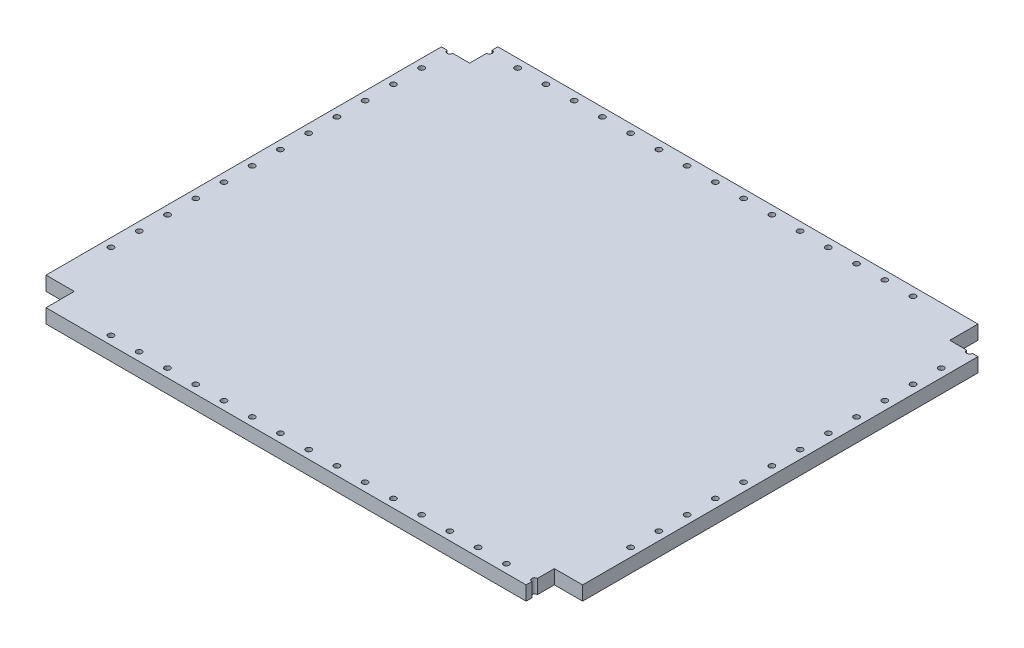
SolidWorks part; units mm, degrees
ref_plane "Front Plane" through (0, 0, 0) normal (0, 0, 1) x (1, 0, 0)
ref_plane "Top Plane" through (0, 0, 0) normal (0, 1, 0) x (1, 0, 0)
ref_plane "Right Plane" through (0, 0, 0) normal (1, 0, 0) x (0, 0, -1)
sketch "Sketch1" plane through (0, 0, 0) normal (0, 1, 0) x (1, 0, 0)
  line L1 (-241.3, -203.2) -> (241.3, -203.2)
  line L2 (-241.3, -203.2) -> (-241.3, 203.2)
  line L3 (-241.3, 203.2) -> (241.3, 203.2)
  line L4 (241.3, -203.2) -> (241.3, 203.2)
  line L5 (-241.3, -203.2) -> (241.3, 203.2) construction
  line L6 (-241.3, 203.2) -> (241.3, -203.2) construction
  point P0 (0, 0)
  dimension "D1" = 482.6
  dimension "D2" = 406.4
extrude "Boss-Extrude1" add sketch "Sketch1" along normal blind 12.7
sketch "Sketch2" plane through (0, 12.7, 0) normal (0, 1, 0) x (1, 0, 0)
  line L0 (241.3, 203.2) -> (-241.3, 203.2) construction
  line L1 (-241.3, 203.2) -> (-241.3, -203.2) construction
  circle A0 centre (-233.68, 177.8) radius 2.5
  dimension "D1" = 5
  dimension "D2" = 25.4
  dimension "D3" = 7.62
extrude "Cut-Extrude1" cut sketch "Sketch2" against normal through all
pattern_linear "LPattern1" count 13 spacing 25.4 along (0, 0, 1) of "Cut-Extrude1"
sketch "Sketch3" plane through (0, 12.7, 0) normal (0, 1, 0) x (1, 0, 0)
  line L0 (241.3, 203.2) -> (-241.3, 203.2) construction
  line L1 (-241.3, 203.2) -> (-241.3, -203.2) construction
  circle A0 centre (-215.9, 195.58) radius 2.5
  dimension "D1" = 5
  dimension "D2" = 7.62
  dimension "D3" = 25.4
extrude "Cut-Extrude2" cut sketch "Sketch3" against normal through all
pattern_linear "LPattern2" count 16 spacing 25.4 along (1, 0, 0) of "Cut-Extrude2"
sketch "Sketch4" plane through (0, 12.7, 0) normal (0, 1, 0) x (1, 0, 0)
  line L0 (241.3, -203.2) -> (241.3, 203.2) construction
  line L1 (241.3, 203.2) -> (-241.3, 203.2) construction
  circle A0 centre (233.68, 177.8) radius 2.5
  dimension "D1" = 5
  dimension "D2" = 7.62
  dimension "D3" = 25.4
extrude "Cut-Extrude3" cut sketch "Sketch4" against normal through all
pattern_linear "LPattern3" count 13 spacing 25.4 along (0, 0, 1) of "Cut-Extrude3"
sketch "Sketch5" plane through (0, 12.7, 0) normal (0, 1, 0) x (1, 0, 0)
  line L0 (241.3, -203.2) -> (241.3, 203.2) construction
  line L1 (-241.3, -203.2) -> (241.3, -203.2) construction
  circle A0 centre (215.9, -195.58) radius 2.5
  dimension "D1" = 5
  dimension "D2" = 25.4
  dimension "D3" = 7.62
extrude "Cut-Extrude4" cut sketch "Sketch5" against normal through all
pattern_linear "LPattern4" count 16 spacing 25.4 along (-1, 0, 0) of "Cut-Extrude4"
sketch "Sketch6" plane through (0, 12.7, 0) normal (0, 1, 0) x (1, 0, 0)
  line L1 (-241.3, 203.2) -> (-215.9, 203.2)
  line L2 (-241.3, 203.2) -> (-241.3, 177.8)
  line L3 (-241.3, 177.8) -> (-215.9, 177.8)
  line L4 (-215.9, 203.2) -> (-215.9, 177.8)
  dimension "D1" = 25.4
  dimension "D2" = 25.4
extrude "Cut-Extrude5" cut sketch "Sketch6" against normal through all
sketch "Sketch7" plane through (0, 12.7, 0) normal (0, 1, 0) x (1, 0, 0)
  line L1 (-241.3, -203.2) -> (-215.9, -203.2)
  line L2 (-241.3, -203.2) -> (-241.3, -177.8)
  line L3 (-241.3, -177.8) -> (-215.9, -177.8)
  line L4 (-215.9, -203.2) -> (-215.9, -177.8)
  dimension "D1" = 25.4
  dimension "D2" = 25.4
extrude "Cut-Extrude6" cut sketch "Sketch7" against normal through all
sketch "Sketch8" plane through (0, 12.7, 0) normal (0, 1, 0) x (1, 0, 0)
  line L1 (241.3, -203.2) -> (215.9, -203.2)
  line L2 (241.3, -203.2) -> (241.3, -177.8)
  line L3 (241.3, -177.8) -> (215.9, -177.8)
  line L4 (215.9, -203.2) -> (215.9, -177.8)
  dimension "D1" = 25.4
  dimension "D2" = 25.4
extrude "Cut-Extrude7" cut sketch "Sketch8" against normal through all
sketch "Sketch9" plane through (0, 12.7, 0) normal (0, 1, 0) x (1, 0, 0)
  line L1 (241.3, 203.2) -> (215.9, 203.2)
  line L2 (241.3, 203.2) -> (241.3, 177.8)
  line L3 (241.3, 177.8) -> (215.9, 177.8)
  line L4 (215.9, 203.2) -> (215.9, 177.8)
  dimension "D1" = 25.4
  dimension "D2" = 25.4
extrude "Cut-Extrude8" cut sketch "Sketch9" against normal through all
